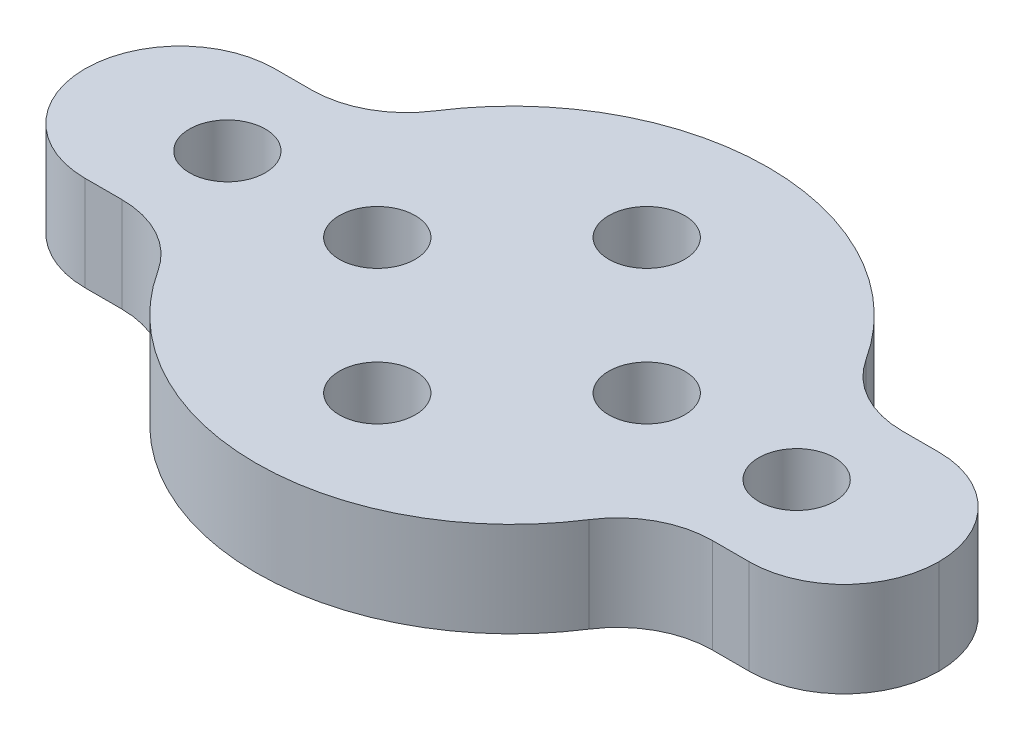
SolidWorks part; units mm, degrees
ref_plane "Front" through (0, 0, 0) normal (0, 0, 1) x (1, 0, 0)
ref_plane "Top" through (0, 0, 0) normal (0, 1, 0) x (1, 0, 0)
ref_plane "Right" through (0, 0, 0) normal (1, 0, 0) x (0, 0, -1)
sketch "Sketch1" plane through (0, 0, 0) normal (0, 1, 0) x (1, 0, 0)
  line L0 (0, 0) -> (0, 12.5189) construction
  line L1 (-22.5, -5) -> (22.5, -5)
  line L2 (-22.5, -5) -> (-22.5, 5)
  line L3 (-22.5, 5) -> (22.5, 5)
  line L4 (22.5, -5) -> (22.5, 5)
  line L5 (-22.5, -5) -> (22.5, 5) construction
  line L6 (-22.5, 5) -> (22.5, -5) construction
  circle A0 centre (0, 0) radius 15 construction
  circle A1 centre (-15, 0) radius 2
  circle A2 centre (15, 0) radius 2
  circle A3 centre (-7.1, 0) radius 2
  circle A4 centre (7.1, 0) radius 2
  circle A5 centre (0, 0) radius 13.5
  circle A6 centre (0, -7.1) radius 2
  circle A7 centre (-7.1, 0) radius 2
  circle A8 centre (0, 7.1) radius 2
  point P26 (0, 0)
  dimension "D1" = 30
  dimension "D2" = 4
  dimension "D6" = 27
  dimension "D3" = 14.2
  dimension "D4" = 10
  dimension "D5" = 45
  dimension "D8" = 14.2
  dimension "D9" = 7.1
  dimension "D7" = 4
extrude "Boss-Extrude1" add sketch "Sketch1" along normal blind 5 contours L1 A5 L3 A4 A3 | A5 L1 L4 L3 A2 | L3 A5 | L1 A5 | A5 L3 L2 L1 A1
fillet "Fillet1" radius 5 4 edges at (-22.5, 2.5, -5) (-22.5, 2.5, 5) (22.5, 2.5, 5) (22.5, 2.5, -5)
fillet "Fillet2" radius 5 4 edges at (-12.5399, 2.5, -5) (12.5399, 2.5, -5) (12.5399, 2.5, 5) (-12.5399, 2.5, 5)
sketch "Sketch3" plane through (0, 0, 0) normal (0, -1, 0) x (1, 0, 0)
  circle A0 centre (-7.1, 0) radius 3.5
  circle A1 centre (7.1, 0) radius 3.5
  dimension "D1" = 7
extrude "Cut-Extrude2" cut sketch "Sketch3" against normal blind 2
sketch "Sketch5" [suppressed] plane through (0, 5, 0) normal (0, 1, 0) x (1, 0, 0)
  circle A0 centre (0, 0) radius 10.5 construction
  dimension "D1" = 21
pattern_circular "CirPattern1" count 2 every 90 about axis through (0, 0, 0) along (0, 1, 0) of "Cut-Extrude2"
